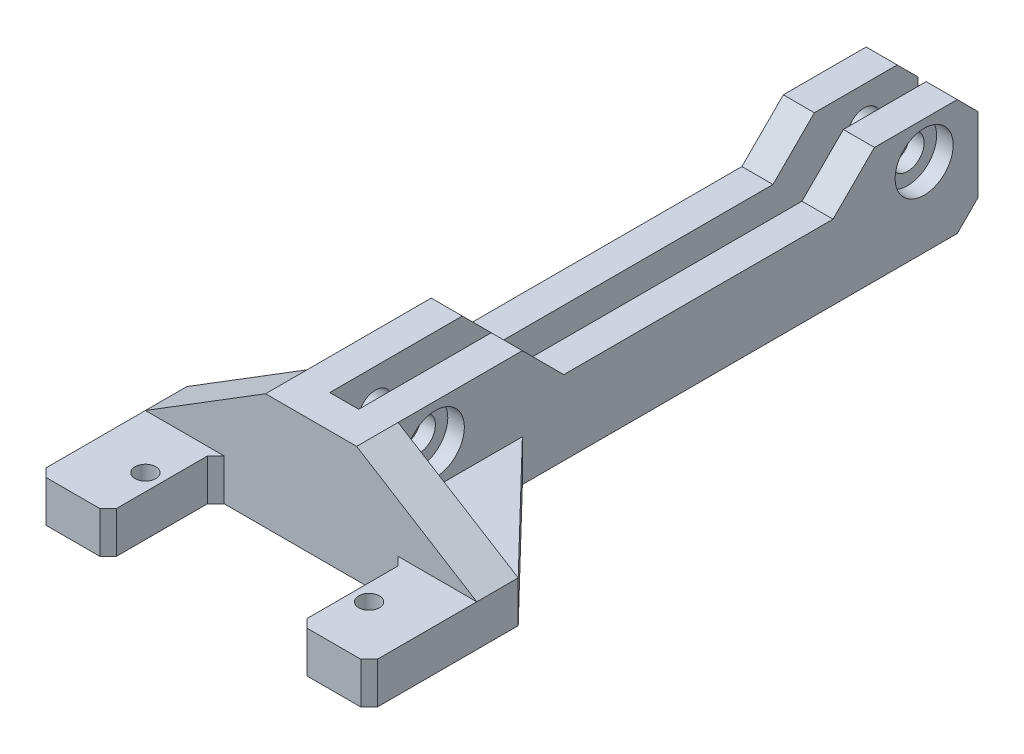
SolidWorks part; units mm, degrees
ref_plane "Front" through (0, 0, 0) normal (0, 0, 1) x (1, 0, 0)
ref_plane "Top" through (0, 0, 0) normal (0, 1, 0) x (1, 0, 0)
ref_plane "Right" through (0, 0, 0) normal (1, 0, 0) x (0, 0, -1)
sketch "Sketch1" plane through (0, 0, 0) normal (0, 1, 0) x (1, 0, 0)
  line L1 (-5.5, -35) -> (5.5, -35)
  line L2 (-5.5, -35) -> (-5.5, 35)
  line L3 (-5.5, 35) -> (5.5, 35)
  line L4 (5.5, -35) -> (5.5, 35)
  line L5 (-5.5, -35) -> (5.5, 35) construction
  line L6 (-5.5, 35) -> (5.5, -35) construction
  line L7 (-20, -53) -> (20, -53)
  line L8 (-20, -53) -> (-20, -35)
  line L9 (-20, -35) -> (20, -35)
  line L10 (20, -53) -> (20, -35)
  line L11 (-20, -53) -> (20, -35) construction
  line L12 (-20, -35) -> (20, -53) construction
  point P0 (0, 0)
  point P6 (0, -44)
  dimension "D1" = 40
  dimension "D2" = 70
  dimension "D3" = 11
  dimension "D4" = 18
extrude "Boss-Extrude1" add sketch "Sketch1" along normal blind 5 contours L7 L10 L9 L1 L8 | L2 L3 L4 L1 region at (0, 0, 44)
sketch "Sketch3" plane through (0, 5, 0) normal (0, 1, 0) x (1, 0, 0)
  line L0 (-20, -53) -> (20, -53) construction
  line L1 (-11.5, -53) -> (11.5, -53)
  line L2 (-11.5, -53) -> (-11.5, -40)
  line L3 (-11.5, -40) -> (11.5, -40)
  line L4 (11.5, -53) -> (11.5, -40)
  line L5 (0, -53) -> (0, -41.827) construction
  dimension "D1" = 23
  dimension "D2" = 13
extrude "Cut-Extrude2" cut sketch "Sketch3" against normal through all
sketch "Sketch4" plane through (0, 5, 0) normal (0, 1, 0) x (1, 0, 0)
  line L0 (-11.5, -40) -> (-11.5, -53) construction
  line L1 (11.5, -53) -> (11.5, -40) construction
  line L2 (0, -40) -> (0, -50.2609) construction
  line L3 (11.5, -40) -> (-11.5, -40) construction
  circle A0 centre (-13.5, -46.5) radius 1.25
  circle A1 centre (13.5, -46.5) radius 1.25
  point P4 (-11.5, -46.5)
  point P5 (11.5, -46.5)
  dimension "D1" = 2.5
  dimension "D2" = 27
extrude "Cut-Extrude3" cut sketch "Sketch4" against normal through all
sketch "Sketch5" plane through (0, 5, 0) normal (0, 1, 0) x (1, 0, 0)
  line L0 (11.5, -40) -> (-11.5, -40) construction
  line L1 (-5.5, 35) -> (5.5, 35)
  line L2 (-5.5, 35) -> (-5.5, -40)
  line L3 (-5.5, -40) -> (5.5, -40)
  line L4 (5.5, 35) -> (5.5, -40)
extrude "Boss-Extrude2" add sketch "Sketch5" along normal blind 9
sketch "Sketch6" plane through (0, 0, 0) normal (0, -1, 0) x (1, 0, 0)
  line L0 (-5.5, -35) -> (5.5, -35) construction
  line L1 (-1.75, -35) -> (1.75, -35)
  line L2 (-1.75, -35) -> (-1.75, 35)
  line L3 (-1.75, 35) -> (1.75, 35)
  line L4 (1.75, -35) -> (1.75, 35)
  line L7 (-20, 35) -> (-5.5, 35) construction
  point P6 (0, -35)
  dimension "D2" = 3.5
extrude "Cut-Extrude4" cut sketch "Sketch6" against normal through all
sketch "Sketch7" plane through (-5.5, 0, 0) normal (-1, 0, 0) x (0, 0, 1)
  line L0 (-35, 14) -> (40, 14) construction
  line L1 (35, 5) -> (35, 0) construction
  circle A0 centre (-28.5, 9.5) radius 2
  circle A1 centre (30.5, 9.5) radius 2
  dimension "D1" = 4
  dimension "D2" = 59
  dimension "D3" = 4.5
  dimension "D4" = 4.5
extrude "Cut-Extrude5" cut sketch "Sketch7" against normal through all
sketch "Sketch8" plane through (0, 0, 40) normal (0, 0, 1) x (1, 0, 0)
  line L0 (-5.5, 14) -> (-20, 5)
rib "Rib2" sketch "Sketch8" sketch "Sketch8" thickness 5 extrusion direction parallel to sketch draft on no parameters "D1"=5
sketch "Sketch9" plane through (0, 0, 40) normal (0, 0, 1) x (1, 0, 0)
  line L0 (5.5, 14) -> (20, 5)
rib "Rib4" sketch "Sketch9" sketch "Sketch9" thickness 5 extrusion direction parallel to sketch draft on no parameters "D1"=5
sketch "Sketch10" plane through (0, 0, 0) normal (0, -1, 0) x (1, 0, 0)
  line L0 (-20, 35) -> (-5.5, 20)
  line L1 (-5.5, 35) -> (-5.5, -35) construction
  line L4 (-20, 35) -> (-5.5, 35) construction
  dimension "D1" = 15
rib "Rib8" sketch "Sketch10" sketch "Sketch10" thickness 5 extrusion direction parallel to sketch draft on no parameters "D1"=5
mirror "Mirror1" about plane through (0, 0, 0) normal (1, 0, 0) of "Rib8"
sketch "Sketch13" plane through (0, 14, 0) normal (0, 1, 0) x (1, 0, 0)
  line L0 (-1.75, -35) -> (-1.75, 35) construction
  line L1 (-5.5, -40) -> (-1.75, -40)
  line L2 (-5.5, -40) -> (-5.5, -20)
  line L3 (-5.5, -20) -> (-1.75, -20)
  line L4 (-1.75, -40) -> (-1.75, -20)
  dimension "D1" = 20
extrude "Boss-Extrude3" [suppressed] add sketch "Sketch13" along normal blind 20
chamfer "Chamfer8" [suppressed] distance 2.5 angle 45
sketch "Sketch14" plane through (5.5, 0, 0) normal (1, 0, 0) x (0, 0, -1)
  line L0 (-40, 14) -> (-40, 5) construction
  line L1 (-20, 14) -> (22.5, 14)
  line L2 (-20, 14) -> (-20, 9)
  line L3 (-20, 9) -> (22.5, 9)
  line L4 (22.5, 14) -> (22.5, 9)
  line L5 (-35, 14) -> (35, 14) construction
  circle A0 centre (28.5, 9.5) radius 2 construction
  dimension "D1" = 6
  dimension "D2" = 5
  dimension "D3" = 20
extrude "Cut-Extrude6" cut sketch "Sketch14" against normal through all
chamfer "Chamfer9" distance 5 angle 45 4 edges at (3.625, 9, -22.5) (-3.625, 9, -22.5) (3.625, 9, 20) (-3.625, 9, 20)
chamfer "Chamfer10" distance 2.5 angle 45 4 edges at (-3.625, 14, -35) (3.625, 14, -35) (3.625, 0, -35) (-3.625, 0, -35)
chamfer "Chamfer11" distance 1 angle 45 4 edges at (-20, 2.5, 53) (-11.5, 2.5, 53) (11.5, 2.5, 53) (20, 2.5, 53)
chamfer "Chamfer12" distance 1 angle 45 2 edges at (11.5, 2.5, 40) (-11.5, 2.5, 40)
sketch "Sketch15" plane through (5.5, 0, 0) normal (1, 0, 0) x (0, 0, -1)
  circle A0 centre (28.5, 9.5) radius 3.5
  circle A1 centre (-30.5, 9.5) radius 3.5
  dimension "D1" = 7
extrude "Cut-Extrude7" cut sketch "Sketch15" against normal blind 2
chamfer "Chamfer14" distance 1 angle 45 2 edges at (0, 0, 35) (0, 14, 35)
